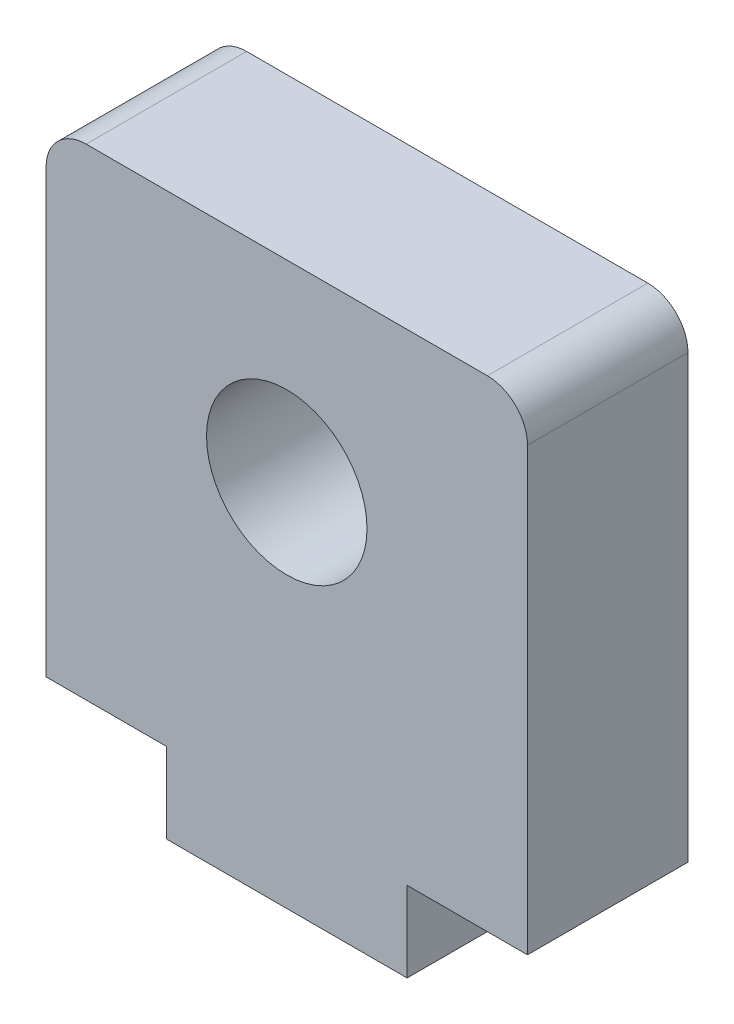
SolidWorks part; units mm, degrees
material "6061-T6 (SS)"
ref_plane "X-Y Datum" through (0, 0, 0) normal (0, 0, 1) x (1, 0, 0)
ref_plane "X-Z Datum" through (0, 0, 0) normal (0, 1, 0) x (1, 0, 0)
ref_plane "Y-Z Datum" through (0, 0, 0) normal (1, 0, 0) x (0, 0, -1)
sketch "Sketch1" plane through (0, 0, 0) normal (0, 0, 1) x (1, 0, 0)
  line L0 (0, 11.1125) -> (0, -11.1125) construction
  line L5 (-9.525, 11.1125) -> (9.525, 11.1125)
  line L6 (-9.525, 11.1125) -> (-9.525, -11.1125)
  line L7 (-9.525, -11.1125) -> (9.525, -11.1125)
  line L8 (9.525, 11.1125) -> (9.525, -11.1125)
  line L9 (-9.525, 11.1125) -> (9.525, -11.1125) construction
  line L10 (-9.525, -11.1125) -> (9.525, 11.1125) construction
  line L11 (-9.525, -7.9375) -> (9.525, -7.9375)
  line L12 (0, -7.9375) -> (0, -11.1125) construction
  line L14 (-4.7625, -7.9375) -> (4.7625, -7.9375)
  line L15 (-4.7625, -7.9375) -> (-4.7625, -11.1125)
  line L16 (-4.7625, -11.1125) -> (4.7625, -11.1125)
  line L17 (4.7625, -7.9375) -> (4.7625, -11.1125)
  line L18 (-4.7625, -7.9375) -> (4.7625, -11.1125) construction
  line L19 (-4.7625, -11.1125) -> (4.7625, -7.9375) construction
  circle A0 centre (0, 3.4925) radius 3.175
  point P0 (0, 0)
  point P14 (0, -9.525)
  dimension "D2" = 6.35
  dimension "D1" = 19.05
  dimension "D3" = 22.225
  dimension "D4" = 7.62
  dimension "D5" = 3.175
  dimension "D6" = 9.525
extrude "Boss-Extrude1" add sketch "Sketch1" along normal blind 6.35 contours L6 L11 L8 L5 A0 | L17 L11 L15 L7 region at (0, 10.8431, 0) region at (0, -9.525, 0)
fillet "Fillet1" radius 1.5875 2 edges at (9.525, 11.1125, 3.175) (-9.525, 11.1125, 3.175)
